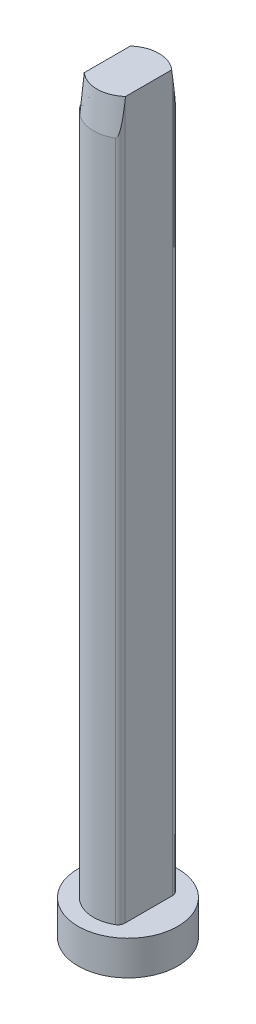
SolidWorks part; units mm, degrees
material "3003 Alloy"
ref_plane "Front Plane" through (0, 0, 0) normal (0, 0, 1) x (1, 0, 0)
ref_plane "Top Plane" through (0, 0, 0) normal (0, 1, 0) x (1, 0, 0)
ref_plane "Right Plane" through (0, 0, 0) normal (1, 0, 0) x (0, 0, -1)
sketch "Sketch5" plane through (0, 0, 0) normal (0, 0, 1) x (1, 0, 0)
  line L0 (0, 0) -> (7.25, 0)
  line L1 (7.25, 0) -> (7.25, 5)
  line L2 (7.25, 5) -> (5, 5)
  line L3 (5, 5) -> (5, 104)
  line L4 (4.5, 109) -> (5, 104)
  line L5 (4.5, 109) -> (0, 109)
  line L6 (0, 109) -> (0, 0) construction
  line L7 (0, 0) -> (0, 109)
  point P3 (4.5, 109)
  dimension "D1" = 7.25
  dimension "D2" = 5
  dimension "D3" = 2.25
  dimension "D4" = 99
  dimension "D5" = 5
  dimension "D6" = 0.5
  dimension "D7" = 4.5
revolve "Revolve1" add sketch "Sketch5" angle 360 about L6
sketch "Sketch6" plane through (0, 109, 0) normal (0, 1, 0) x (1, 0, 0)
  line L1 (3, 4) -> (3, -4)
  line L2 (-3, 4) -> (-3, -4)
  arc A2 (-3, 4) -> (-3, -4) centre (0, 0) ccw
  arc A3 (3, -4) -> (3, 4) centre (0, 0) ccw
  dimension "D1" = 10
  dimension "D2" = 3
  dimension "D4" = 3
extrude "Cut-Extrude1" cut sketch "Sketch6" against normal blind 5
sketch "Sketch7" plane through (0, 104, 0) normal (0, 1, 0) x (1, 0, 0)
  line L0 (3, -4) -> (3, 4)
  line L1 (3, 4) -> (3, -4) construction
  arc A0 (3, -4) -> (3, 4) centre (0, 0) ccw
extrude "Cut-Extrude2" cut sketch "Sketch7" against normal up to surface (99 mm away) up to face at (-5, 5, 0)
fillet "Fillet1" radius 1 2 edges at (3, 54.5, 4) (3, 54.5, -4)
